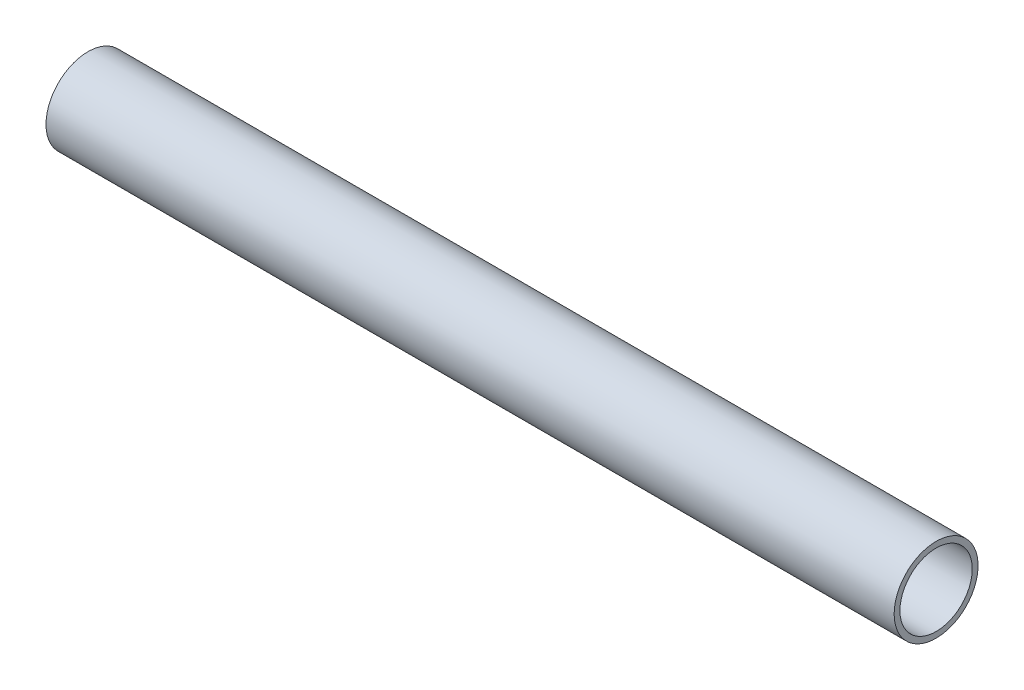
SolidWorks part; units mm, degrees
material "PVC Rigid"
ref_plane "Front Plane" through (0, 0, 0) normal (0, 0, 1) x (1, 0, 0)
ref_plane "Top Plane" through (0, 0, 0) normal (0, 1, 0) x (1, 0, 0)
ref_plane "Right Plane" through (0, 0, 0) normal (1, 0, 0) x (0, 0, -1)
sketch "Sketch1" plane through (0, 0, 0) normal (1, 0, 0) x (0, 0, -1)
  circle A0 centre (0, 0) radius 30.1625
  circle A1 centre (0, 0) radius 25.9969
  dimension "D1" = 60.325
  dimension "D2" = 51.9938
extrude "Boss-Extrude1" add sketch "Sketch1" along normal blind 609.6
